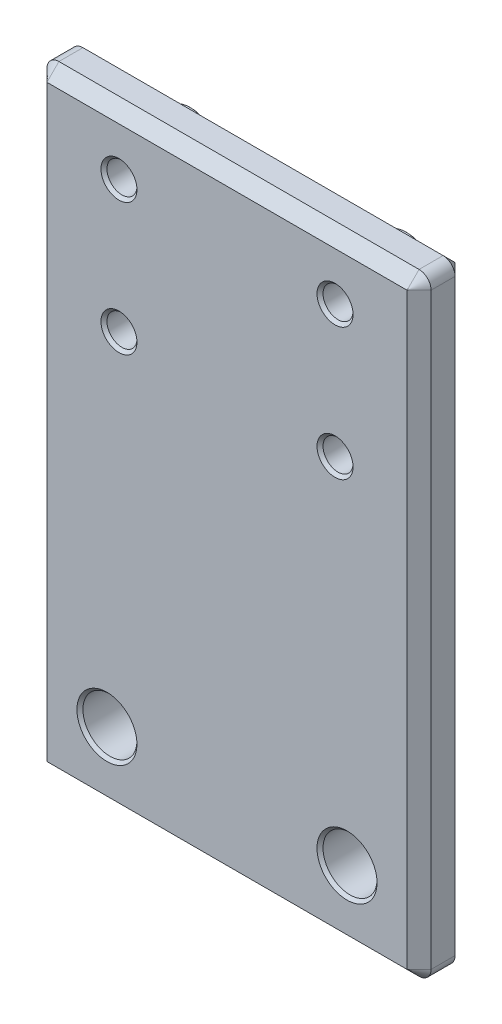
SolidWorks part; units mm, degrees
material "ABS"
ref_plane "Front Plane" through (0, 0, 0) normal (0, 0, 1) x (1, 0, 0)
ref_plane "Top Plane" through (0, 0, 0) normal (0, 1, 0) x (1, 0, 0)
ref_plane "Right Plane" through (0, 0, 0) normal (1, 0, 0) x (0, 0, -1)
ref_axis "X Axis" through (88.99, 0, 0) along (-1, 0, 0)
ref_axis "Y Axis" through (0, 55, 0) along (0, -1, 0)
ref_axis "Z Axis" through (0, 0, -88.99) along (0, 0, 1)
sketch "Sketch1" plane through (0, 0, 0) normal (0, 0, 1) x (1, 0, 0)
  line L1 (-16, -40.5) -> (16, -40.5)
  line L2 (-16, -40.5) -> (-16, 10.5)
  line L3 (-16, 10.5) -> (16, 10.5)
  line L4 (16, -40.5) -> (16, 10.5)
  line L5 (0, 10.5) -> (0, -40.5) construction
  line L6 (-16, -15) -> (16, -15) construction
  line L7 (9, -5.5) -> (-9, -5.5) construction
  line L8 (9, -5.5) -> (9, 5.5) construction
  line L9 (9, 5.5) -> (-9, 5.5) construction
  line L10 (-9, -5.5) -> (-9, 5.5) construction
  line L11 (0, 5.5) -> (0, -5.5) construction
  line L12 (9, 0) -> (-9, 0) construction
  line L15 (9, 10.5) -> (16, 10.5) construction
  line L16 (16, 5.5) -> (16, 10.5) construction
  line L17 (10, -34.5) -> (-10, -34.5) construction
  line L18 (10, -34.5) -> (10, -40.5) construction
  line L19 (10, -40.5) -> (-10, -40.5) construction
  line L20 (-10, -34.5) -> (-10, -40.5) construction
  line L21 (0, -40.5) -> (0, -34.5) construction
  line L22 (10, -37.5) -> (-10, -37.5) construction
  circle A0 centre (-9, 5.5) radius 2.25
  circle A1 centre (-9, -5.5) radius 2.25
  circle A2 centre (9, -5.5) radius 2.25
  circle A3 centre (9, 5.5) radius 2.25
  point P0 (0, -15)
  point P4 (0, 0)
  point P18 (0, -37.5)
  dimension "D8" = 4.5
  dimension "D1" = 51
  dimension "D2" = 32
  dimension "D3" = 11
  dimension "D4" = 18
  dimension "D5" = 6
  dimension "D6" = 20
  dimension "D7" = 5
extrude "Boss-Extrude1" add sketch "Sketch1" along normal blind 4 contours L1 L4 L3 L2 A3 A2 A1 A0 | A0 | A3 | A1 | A2 region at (0, -15.6084, 0) region at (-9, 5.5, 0) region at (-9, -5.5, 0) region at (9, -5.5, 0) region at (9, 5.5, 0)
extrude "Boss-Extrude2" add sketch "Sketch1<3>" against normal blind 2 contours A0 | A3 | A1 | A2 region at (-9, 5.5, 0) region at (-9, -5.5, 0) region at (9, -5.5, 0) region at (9, 5.5, 0)
sketch "Sketch1<3>" plane through (0, 0, 0) normal (0, 0, 1) x (1, 0, 0) same geometry as "Sketch1"
sketch "Sketch6" plane through (0, 0, -2) normal (0, 0, 1) x (1, 0, 0)
  point P0 (-9, 5.5)
  point P3 (-9, -5.5)
  point P6 (9, -5.5)
  point P9 (9, 5.5)
hole_wizard "Ø2.5mm Dowel Hole1" positions "Sketch6" profile "Sketch5" hole size "Ø2.5" standard "ANSI Metric" end condition through all
sketch "Sketch5" plane through (-9, 5.5, -2) normal (1, 0, 0) x (0, 1, 0)
  line L0 (0, 0) -> (0, 6)
  line L1 (0, 6) -> (1.5, 6)
  line L2 (1.25, 5.75) -> (1.25, 0.25)
  line L3 (1.25, 0.25) -> (1.5, 0)
  line L5 (1.5, 0) -> (0, 0)
  line L6 (-1.25, 0.25) -> (-1.5, 0) construction
  line L7 (1.5, 6) -> (1.25, 5.75)
  line L8 (-1.5, 6) -> (-1.25, 5.75) construction
  line L11 (0, -6.35) -> (0, 107.95) construction
  dimension "Thru Hole Dia." = 2.5
  dimension "Thru Hole Depth" = 6
  dimension "Near C'Sink Dia." = 3
  dimension "Near C'Sink Angle" = 90
  dimension "Far C'Sink Dia." = 3
  dimension "Far C'Sink Angle" = 90
sketch "Sketch9" plane through (0, 0, 0) normal (0, 0, 1) x (1, 0, 0)
  point P0 (-10, -34.5)
  point P3 (10, -34.5)
hole_wizard "M4 Clearance Hole1" positions "Sketch9" profile "Sketch8" hole size "M4" standard "ANSI Metric" end condition through all
sketch "Sketch8" plane through (-10, -34.5, 0) normal (1, 0, 0) x (0, 1, 0)
  line L0 (0, 0) -> (0, 4)
  line L1 (0, 4) -> (2.5, 4)
  line L2 (2.25, 3.75) -> (2.25, 0.25)
  line L3 (2.25, 0.25) -> (2.5, 0)
  line L5 (2.5, 0) -> (0, 0)
  line L6 (-2.25, 0.25) -> (-2.5, 0) construction
  line L7 (2.5, 4) -> (2.25, 3.75)
  line L8 (-2.5, 4) -> (-2.25, 3.75) construction
  line L11 (0, -6.35) -> (0, 107.95) construction
  dimension "Thru Hole Dia." = 4.5
  dimension "Thru Hole Depth" = 4
  dimension "Near C'Sink Dia." = 5
  dimension "Near C'Sink Angle" = 90
  dimension "Far C'Sink Dia." = 5
  dimension "Far C'Sink Angle" = 90
fillet "Fillet1" radius 1 4 edges at (16, 10.5, 2) (16, -40.5, 2) (-16, -40.5, 2) (-16, 10.5, 2)
chamfer "Chamfer1" distance 1 angle 45 16 edges at (0, -40.5, 4) (-15.7071, -40.2071, 4) (15.7071, -40.2071, 4) (-16, -15, 4) (16, -15, 4) (-15.7071, 10.2071, 4) (15.7071, 10.2071, 4) (0, 10.5, 4) (0, -40.5, 0) (-15.7071, -40.2071, 0) (15.7071, -40.2071, 0) (-16, -15, 0) (16, -15, 0) (-15.7071, 10.2071, 0) (15.7071, 10.2071, 0) (0, 10.5, 0)
chamfer "Chamfer2" distance 0.1 angle 45 8 edges at (11.25, -5.5, 0) (11.25, -5.5, -2) (11.25, 5.5, 0) (11.25, 5.5, -2) (-6.75, -5.5, 0) (-6.75, -5.5, -2) (-6.75, 5.5, 0) (-6.75, 5.5, -2)
